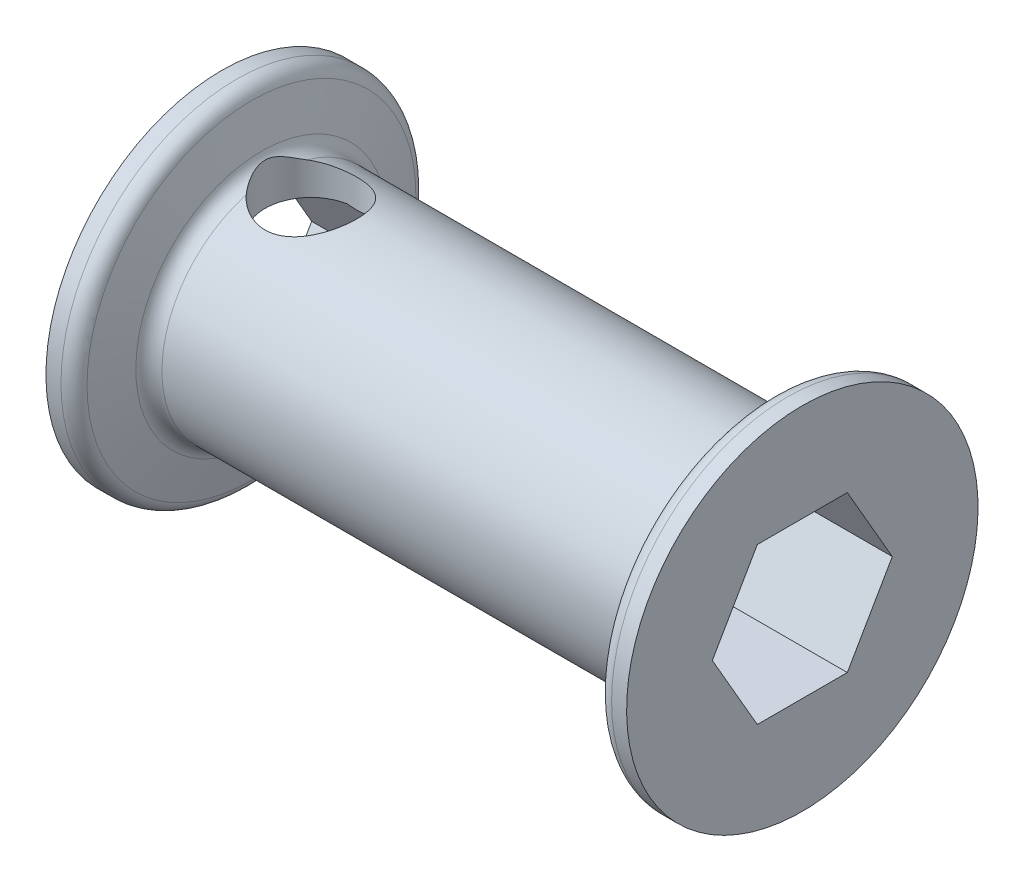
SolidWorks part; units mm, degrees
ref_plane "Front Plane" through (0, 0, 0) normal (0, 0, 1) x (1, 0, 0)
ref_plane "Top Plane" through (0, 0, 0) normal (0, 1, 0) x (1, 0, 0)
ref_plane "Right Plane" through (0, 0, 0) normal (1, 0, 0) x (0, 0, -1)
sketch "Sketch1" plane through (0, 0, 0) normal (0, 0, 1) x (1, 0, 0)
  line L0 (0, 0) -> (48.26, 0)
  line L1 (48.26, 0) -> (48.26, 14.605)
  line L2 (48.26, 14.605) -> (46.0375, 14.605)
  line L3 (46.0375, 14.605) -> (44.6763, 9.525)
  line L4 (44.6763, 9.525) -> (3.5837, 9.525)
  line L5 (3.5837, 9.525) -> (2.2225, 14.605)
  line L6 (2.2225, 14.605) -> (0, 14.605)
  line L7 (0, 14.605) -> (0, 0)
  line L8 (48.26, 0) -> (36.7691, 0) construction
  dimension "D1" = 48.26
  dimension "D2" = 5.08
  dimension "D3" = 5.08
  dimension "D4" = 19.05
  dimension "D5" = 15
  dimension "D6" = 2.2225
revolve "Revolve1" add sketch "Sketch1" angle 360 about L8
sketch "Sketch2" plane through (0, 0, 0) normal (-1, 0, 0) x (0, 0, 1)
  line L0 (-14.605, 0) -> (14.605, 0) construction
  line L1 (7.479, 0) -> (3.7395, 6.477)
  line L2 (3.7395, 6.477) -> (-3.7395, 6.477)
  line L3 (-3.7395, 6.477) -> (-7.479, 0)
  line L4 (-7.479, 0) -> (-3.7395, -6.477)
  line L5 (-3.7395, -6.477) -> (3.7395, -6.477)
  line L6 (3.7395, -6.477) -> (7.479, 0)
  circle A0 centre (0, 0) radius 6.477 construction
  circle A2 centre (0, 0) radius 14.605 construction
  dimension "D1" = 12.954
  dimension "D2" = 7.126
extrude "Cut-Extrude1" cut sketch "Sketch2" against normal through all
fillet "Fillet1" radius 1.27 4 edges at (3.5837, 9.525, 0) (2.2225, 14.605, 0) (46.0375, 14.605, 0) (44.6763, 9.525, 0)
sketch "Sketch3" plane through (0, 0, 0) normal (0, 0, 1) x (1, 0, 0)
  line L6 (48.26, -14.605) -> (48.26, 14.605) construction
  line L12 (0, 0) -> (31.817, 0) construction
  line L13 (48.26, 14.605) -> (47.012, 14.605) construction
  line L14 (47.012, -14.605) -> (48.26, -14.605) construction
  line L15 (9.3207, -14.605) -> (7.4157, -14.605)
  line L16 (9.3207, -14.605) -> (9.3207, -0.0253)
  line L17 (7.4157, -14.605) -> (7.4157, 14.605)
  line L18 (11.2257, -0.0253) -> (9.3207, -0.0253)
  line L19 (7.4157, 14.605) -> (7.4157, 15.4744) construction
  line L20 (7.4157, 14.605) -> (11.2257, 14.605)
  line L21 (11.2257, 14.605) -> (11.2257, -0.0253)
  dimension "D1" = 7.62
  dimension "D2" = 3.81
  dimension "D3" = 40.8443
  dimension "D4" = 0.0506
revolve "Cut-Revolve1" cut sketch "Sketch3" angle 360 about L19
